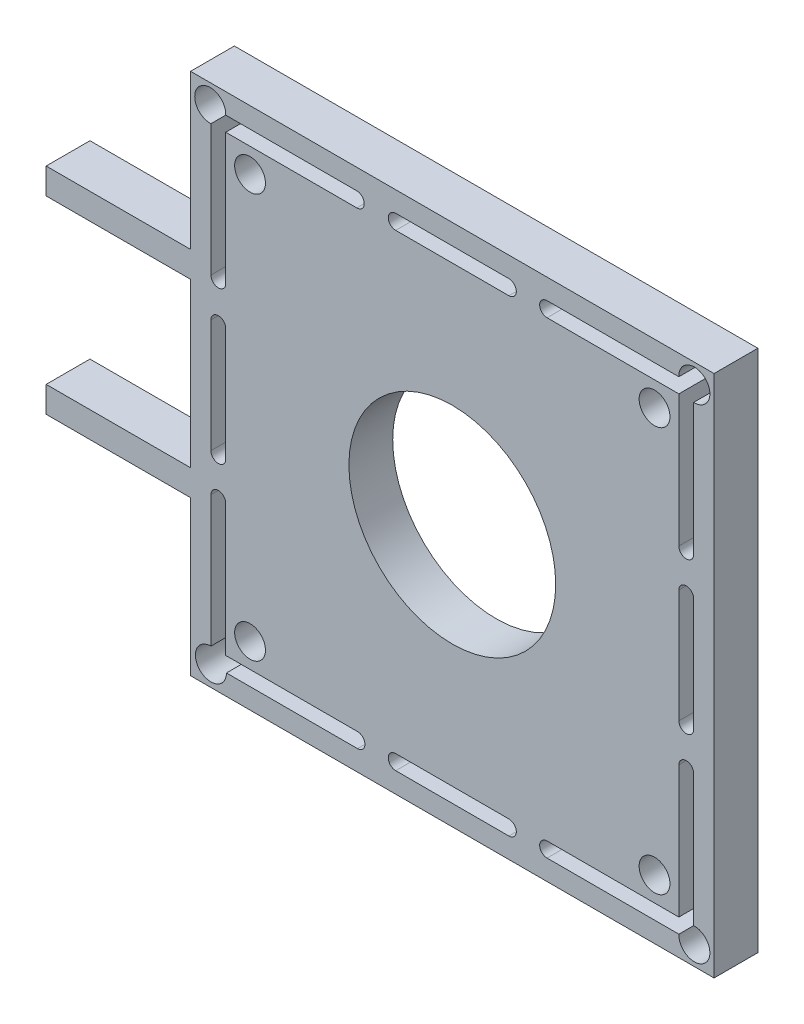
SolidWorks part; units mm, degrees
ref_plane "Front Plane" through (0, 0, 0) normal (0, 0, 1) x (1, 0, 0)
ref_plane "Top Plane" through (0, 0, 0) normal (0, 1, 0) x (1, 0, 0)
ref_plane "Right Plane" through (0, 0, 0) normal (1, 0, 0) x (0, 0, -1)
sketch "Sketch1" plane through (0, 0, 0) normal (0, 0, 1) x (1, 0, 0)
  line L1 (0, 37.9349) -> (37.9349, 37.9349)
  line L2 (0, 37.9349) -> (0, 0)
  line L3 (0, 0) -> (37.9349, 0)
  line L4 (37.9349, 37.9349) -> (37.9349, 0)
  dimension "D1" = 37.9349
extrude "Boss-Extrude1" add sketch "Sketch1" along normal blind 3.175
sketch "Sketch9" plane through (0, 0, 3.175) normal (0, 0, 1) x (1, 0, 0)
  line L0 (33.6232, 33.6232) -> (35.9219, 33.6232) construction
  line L1 (0, 0) -> (37.9349, 0) construction
  line L2 (2.5493, 18.9674) -> (1.4766, 18.9675) construction
  line L3 (33.6232, 35.922) -> (33.6232, 33.6232) construction
  line L4 (0, 37.9349) -> (0, 0) construction
  line L5 (35.3856, 12.1002) -> (36.4583, 12.1002) construction
  line L6 (4.3117, 35.9219) -> (4.3117, 33.6232) construction
  line L7 (2.013, 33.6232) -> (4.3117, 33.6232) construction
  line L8 (4.3117, 2.013) -> (4.3117, 4.3117) construction
  line L9 (2.0129, 4.3117) -> (4.3117, 4.3117) construction
  line L10 (35.9219, 4.3117) -> (33.6232, 4.3117) construction
  line L11 (33.6232, 2.013) -> (33.6232, 4.3117) construction
  line L12 (35.3856, 12.1002) -> (35.3856, 2.5493)
  line L13 (35.3856, 2.5493) -> (25.8347, 2.5493)
  line L14 (35.3856, 1.4766) -> (25.8347, 1.4766)
  line L15 (35.3856, 36.4583) -> (25.8347, 36.4583)
  line L16 (37.9349, 37.9349) -> (0, 37.9349) construction
  line L17 (12.0489, 36.4583) -> (2.5493, 36.4583)
  line L18 (12.0489, 36.4583) -> (12.0489, 35.3856) construction
  line L19 (12.0489, 35.3856) -> (2.5493, 35.3856)
  line L20 (35.922, 35.9219) -> (2.0129, 35.9219) construction
  line L21 (23.0695, 36.4583) -> (14.8653, 36.4583)
  line L22 (35.922, 35.9219) -> (35.922, 2.013) construction
  line L23 (35.922, 2.013) -> (2.013, 2.013) construction
  line L24 (2.0129, 35.9219) -> (2.013, 2.013) construction
  line L25 (18.9674, 37.9349) -> (18.9674, 0) construction
  line L26 (23.0695, 36.4583) -> (23.0695, 35.3856) construction
  line L27 (23.0695, 35.3856) -> (14.8653, 35.3856)
  line L28 (0, 0) -> (37.9349, 0) construction
  line L29 (25.8347, 2.5493) -> (25.8347, 1.4766) construction
  line L30 (14.8653, 36.4583) -> (14.8653, 35.3856) construction
  line L31 (35.3856, 2.5493) -> (36.4583, 2.5493) construction
  line L32 (35.922, 18.9674) -> (2.013, 18.9674) construction
  line L33 (2.5493, 36.4583) -> (2.5493, 35.3856) construction
  line L34 (2.5493, 35.3856) -> (1.4766, 35.3856) construction
  line L35 (2.5493, 12.1002) -> (1.4766, 12.1002) construction
  line L36 (36.4583, 12.1002) -> (36.4583, 2.5493)
  line L37 (35.3856, 35.3856) -> (25.8347, 35.3856)
  line L38 (2.5493, 35.3856) -> (2.5493, 25.886)
  line L39 (12.1002, 2.5493) -> (12.1002, 1.4766) construction
  line L42 (25.8347, 36.4583) -> (25.8347, 35.3856) construction
  line L43 (35.3856, 35.3856) -> (36.4583, 35.3856) construction
  line L44 (35.3856, 35.3856) -> (35.3856, 25.8347)
  line L45 (35.3856, 25.8347) -> (36.4583, 25.8347) construction
  line L46 (36.4583, 35.3856) -> (36.4583, 25.8347)
  line L47 (2.5493, 25.886) -> (1.4766, 25.886) construction
  line L48 (1.4766, 35.3856) -> (1.4766, 25.886)
  line L49 (2.5493, 23.0696) -> (1.4766, 23.0696) construction
  line L50 (2.5493, 23.0696) -> (2.5493, 14.8654)
  line L51 (2.5493, 14.8654) -> (1.4766, 14.8654) construction
  line L52 (1.4766, 23.0696) -> (1.4766, 14.8654)
  line L53 (36.4583, 18.9675) -> (35.3856, 18.9675) construction
  line L54 (36.4583, 23.0695) -> (35.3856, 23.0695) construction
  line L55 (36.4583, 23.0695) -> (36.4583, 14.8654)
  line L56 (36.4583, 14.8654) -> (35.3856, 14.8654) construction
  line L57 (35.3856, 23.0695) -> (35.3856, 14.8654)
  line L58 (18.9674, 36.4583) -> (18.9674, 35.3856) construction
  line L59 (18.9674, 2.5493) -> (18.9674, 1.4766) construction
  line L60 (23.0695, 2.5493) -> (14.8653, 2.5493)
  line L61 (23.0695, 2.5493) -> (23.0695, 1.4766) construction
  line L62 (23.0695, 1.4766) -> (14.8653, 1.4766)
  line L63 (14.8653, 2.5493) -> (14.8653, 1.4766) construction
  line L68 (2.5493, 12.1002) -> (2.5493, 2.5493)
  line L69 (1.4766, 12.1002) -> (1.4766, 2.6006)
  line L70 (2.5493, 2.5493) -> (12.1002, 2.5493)
  line L71 (2.6006, 1.4766) -> (12.1002, 1.4766)
  line L75 (12.1002, 2.013) -> (12.6365, 2.013) construction
  line L76 (2.013, 2.013) -> (2.013, 0) construction
  line L77 (0, 2.0129) -> (2.013, 2.013) construction
  circle A0 centre (33.6232, 33.6232) radius 1.1176
  circle A1 centre (4.3117, 33.6232) radius 1.1176
  circle A2 centre (4.3117, 4.3117) radius 1.1176
  circle A3 centre (33.6232, 4.3117) radius 1.1176
  arc A4 (25.8347, 1.4766) -> (25.8347, 2.5493) centre (25.8347, 2.013) cw
  arc A5 (36.4583, 2.5493) -> (35.3856, 1.4766) centre (36.5084, 1.4265) cw
  arc A6 (14.8653, 36.4583) -> (14.8653, 35.3856) centre (14.8653, 35.9219) ccw
  arc A7 (23.0695, 36.4583) -> (23.0695, 35.3856) centre (23.0695, 35.9219) cw
  arc A8 (1.4766, 2.6006) -> (2.6006, 1.4766) centre (1.4766, 1.4766) ccw
  arc A9 (36.4583, 12.1002) -> (35.3856, 12.1002) centre (35.9219, 12.1002) ccw
  arc A10 (12.0489, 35.3856) -> (12.0489, 36.4583) centre (12.0489, 35.9219) ccw
  arc A11 (1.4766, 35.3856) -> (2.5493, 36.4583) centre (1.4265, 36.5084) cw
  arc A12 (36.4583, 25.8347) -> (35.3856, 25.8347) centre (35.922, 25.8347) cw
  arc A13 (25.8347, 35.3856) -> (25.8347, 36.4583) centre (25.8347, 35.9219) cw
  arc A14 (36.4583, 35.3856) -> (35.3856, 36.4583) centre (36.5084, 36.5084) ccw
  arc A15 (2.5493, 25.886) -> (1.4766, 25.886) centre (2.013, 25.886) cw
  arc A16 (2.5493, 23.0696) -> (1.4766, 23.0696) centre (2.0129, 23.0695) ccw
  arc A17 (1.4766, 14.8654) -> (2.5493, 14.8654) centre (2.0129, 14.8654) ccw
  arc A18 (1.4766, 12.1002) -> (2.5493, 12.1002) centre (2.0129, 12.1002) cw
  arc A19 (12.1002, 2.5493) -> (12.1002, 1.4766) centre (12.1002, 2.013) cw
  arc A20 (36.4583, 23.0695) -> (35.3856, 23.0695) centre (35.922, 23.0695) ccw
  arc A21 (36.4583, 14.8654) -> (35.3856, 14.8654) centre (35.922, 14.8653) cw
  arc A22 (14.8653, 2.5493) -> (14.8653, 1.4766) centre (14.8654, 2.0129) ccw
  arc A23 (23.0695, 1.4766) -> (23.0695, 2.5493) centre (23.0695, 2.0129) ccw
  point P47 (18.9674, 18.9674)
  point P66 (2.0129, 18.9674)
  point P89 (35.922, 18.9674)
  dimension "D1" = 9.4996
  dimension "D3" = 2.013
  dimension "D4" = 2.2352
  dimension "D6" = 8.2042
  dimension "D5" = 1.1239
  dimension "D7" = 1.0727
  dimension "D2" = 2.2987
extrude "Cut-Extrude2" cut sketch "Sketch9" against normal up to surface (3.175 mm away) up to face at (18.9674, 18.9675, 0)
sketch "Sketch10" plane through (0, 0, 0) normal (0, 0, -1) x (-1, 0, 0)
  line L0 (-18.9674, 37.9349) -> (-18.9674, 0) construction
  line L1 (-37.9349, 37.9349) -> (0, 37.9349) construction
  line L2 (0, 0) -> (-37.9349, 0) construction
  circle A0 centre (-18.9674, 18.9674) radius 7.493
  dimension "D1" = 14.986
extrude "Cut-Extrude3" cut sketch "Sketch10" against normal up to surface (3.175 mm away) up to face at (18.9674, 2.0129, 3.175)
sketch "Sketch11" plane through (0, 0, 3.175) normal (0, 0, 1) x (1, 0, 0)
  line L0 (0, 11.176) -> (0, 0) construction
  line L1 (-10.4648, 26.7589) -> (0, 26.7589)
  line L2 (-10.4648, 26.7589) -> (-10.4648, 24.8793)
  line L3 (-10.4648, 24.8793) -> (0, 24.8793)
  line L4 (0, 26.7589) -> (0, 24.8793)
  line L5 (0, 37.9349) -> (0, 0) construction
  line L6 (0, 37.9349) -> (0, 26.7589) construction
  line L7 (-10.4648, 13.0556) -> (0, 13.0556)
  line L8 (-10.4648, 13.0556) -> (-10.4648, 11.176)
  line L9 (-10.4648, 11.176) -> (0, 11.176)
  line L10 (0, 13.0556) -> (0, 11.176)
  dimension "D1" = 1.8796
  dimension "D2" = 10.4648
  dimension "D3" = 11.176
extrude "Boss-Extrude2" add sketch "Sketch11" against normal up to surface (3.175 mm away) up to face at (11.4744, 18.9674, 0)
